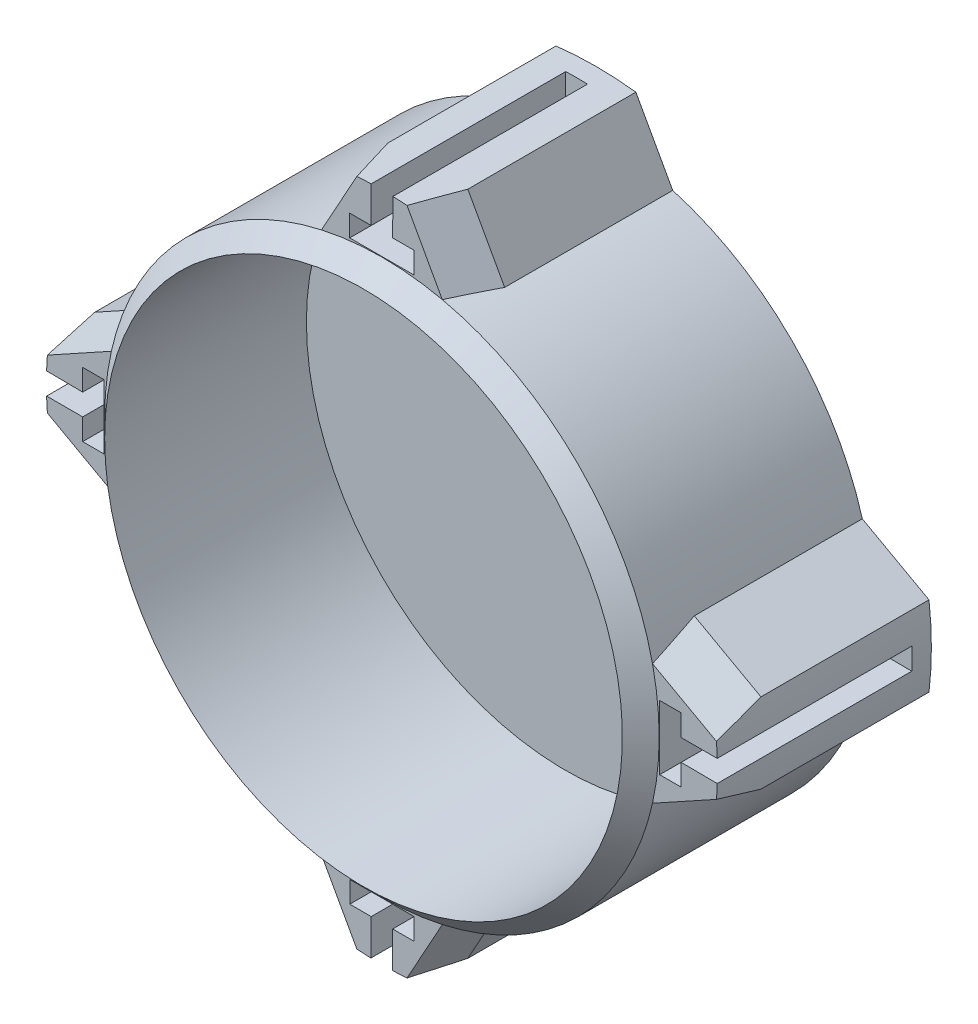
SolidWorks part; units mm, degrees
note: '?' marks a value the reader was unsure of.
ref_plane "Front Plane" through (0, 0, 0) normal (0, 0, 1) x (1, 0, 0)
ref_plane "Top Plane" through (0, 0, 0) normal (0, 1, 0) x (1, 0, 0)
ref_plane "Right Plane" through (0, 0, 0) normal (1, 0, 0) x (0, 0, -1)
sketch "Sketch1" plane through (0, 0, 0) normal (0, 0, 1) x (1, 0, 0)
  circle A0 centre (0, 0) radius 84.5
  circle A1 centre (0, 0) radius 90.5
  dimension "D1" = 169
  dimension "D2" = 181
extrude "Boss-Extrude1" add sketch "Sketch1" along normal blind 76.35
sketch "Sketch2" plane through (0, 0, 76.35) normal (0, 0, 1) x (1, 0, 0)
ref_axis "Axis1" through (0, 0, 76.35) along (0, 0, -1)?
chamfer "Chamfer1" distance 6.5 angle 45 1 edges at (90.5, 0, 76.35)
ref_plane "Plane1" through (90.5, 0, 0) normal (1, 0, 0) x (0, 0, -1)
sketch "Sketch4" plane through (90.5, 0, 0) normal (1, 0, 0) x (0, 0, -1)
  line L0 (-69.85, -90.5) -> (-69.85, 90.5) construction
  line L1 (-69.85, 25.4001) -> (0, 25.4001)
  line L2 (-69.85, 25.4001) -> (-69.85, -25.3999)
  line L3 (-69.85, -25.3999) -> (0, -25.3999)
  line L4 (0, 25.4001) -> (0, -25.3999)
  dimension "D1" = 69.85
  dimension "D2" = 50.8
wrap "Wrap12" sketch "Sketch4" wrap type emboss source sketch "Sketch4" thickness 19 face at (90.5, 0, 69.85) parameters "D1"=19
sketch "Sketch12" plane through (0, 0, 69.85) normal (0, 0, 1) x (1, 0, 0)
  line L1 (122.7067, -0.2012) -> (122.7067, 3.5079)
  line L2 (97.6714, 3.5079) -> (97.6714, 10.5031)
  line L3 (97.6714, 10.5031) -> (90.6686, 10.5031)
  line L4 (90.6686, 10.5031) -> (90.6686, -10.4921)
  line L5 (90.6686, -10.4921) -> (97.6714, -10.4921)
  line L6 (97.6714, 3.5079) -> (122.7067, 3.5079)
  line L7 (122.7067, -0.2012) -> (122.7067, -3.7041)
  line L8 (122.7067, -3.7041) -> (97.6714, -3.4921)
  line L9 (97.6714, -3.4921) -> (97.6714, -10.4921)
  dimension "D1" = 7
  dimension "D2" = 3.5029
  dimension "D3" = 3.7091
  dimension "D4" = 20.9953
extrude "Cut-Extrude1" cut sketch "Sketch12" against normal blind 63.5 contours L7 L8 L9 L5 L4 L3 L2 L6 L1
chamfer "Chamfer2" distance 19 angle 45 2 edges at (105.2155, -30.3306, 34.925) (105.2155, 30.3308, 34.925)
chamfer "Chamfer5" distance 15 angle 15 2 edges at (97.8395, -19.0566, 69.85) (97.8395, 19.0568, 69.85)
pattern_circular "CirPattern6" count 4 over 360 about axis through (0, 0, 0) along (0, 0, 1) of bodies 104
sketch "Sketch15" plane through (0, 0, 0) normal (0, 0, -1) x (-1, 0, 0)
  circle A0 centre (0, 0) radius 84.5
extrude "Boss-Extrude2" add sketch "Sketch15" against normal blind 10
sketch "Sketch13" [suppressed] plane through (-0.0226, -2.6651, 0) normal (0.0085, 1, 0) x (1, -0.0085, 0)
sketch "Sketch14" plane through (0, 0, 0) normal (0, 0, -1) x (-1, 0, 0)
